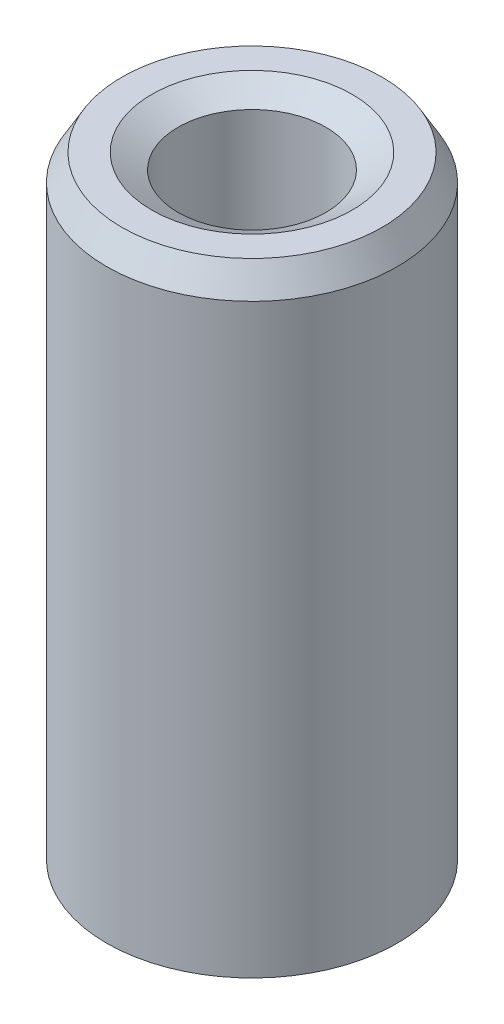
SolidWorks part; units mm, degrees
ref_plane "Front Plane" through (0, 0, 0) normal (0, 0, 1) x (1, 0, 0)
ref_plane "Top Plane" through (0, 0, 0) normal (0, 1, 0) x (1, 0, 0)
ref_plane "Right Plane" through (0, 0, 0) normal (1, 0, 0) x (0, 0, -1)
sketch "Sketch1" plane through (0, 0, 0) normal (0, 1, 0) x (1, 0, 0)
  circle A0 centre (0, 0) radius 7.5
  dimension "SLEEVE_OD" = 15
extrude "Boss-Extrude1" add sketch "Sketch1" along normal blind 32.3776
sketch "Sketch2" plane through (0, 0, 0) normal (0, 1, 0) x (1, 0, 0)
  circle A0 centre (0, 0) radius 3.8124
  dimension "BORE_D" = 7.6248
extrude "Cut-Extrude1" cut sketch "Sketch2" along normal through all
chamfer "Chamfer1" distance 1.3608 angle 30 4 edges at (0, 32.3776, 3.8124) (0, 0, 3.8124) (0, 0, 7.5) (0, 32.3776, 7.5) first distance on face at (0, 32.3776, 3.8124) first distance on face at (0, 0, 3.8124) first distance on face at (0, 32.3776, 7.5)
